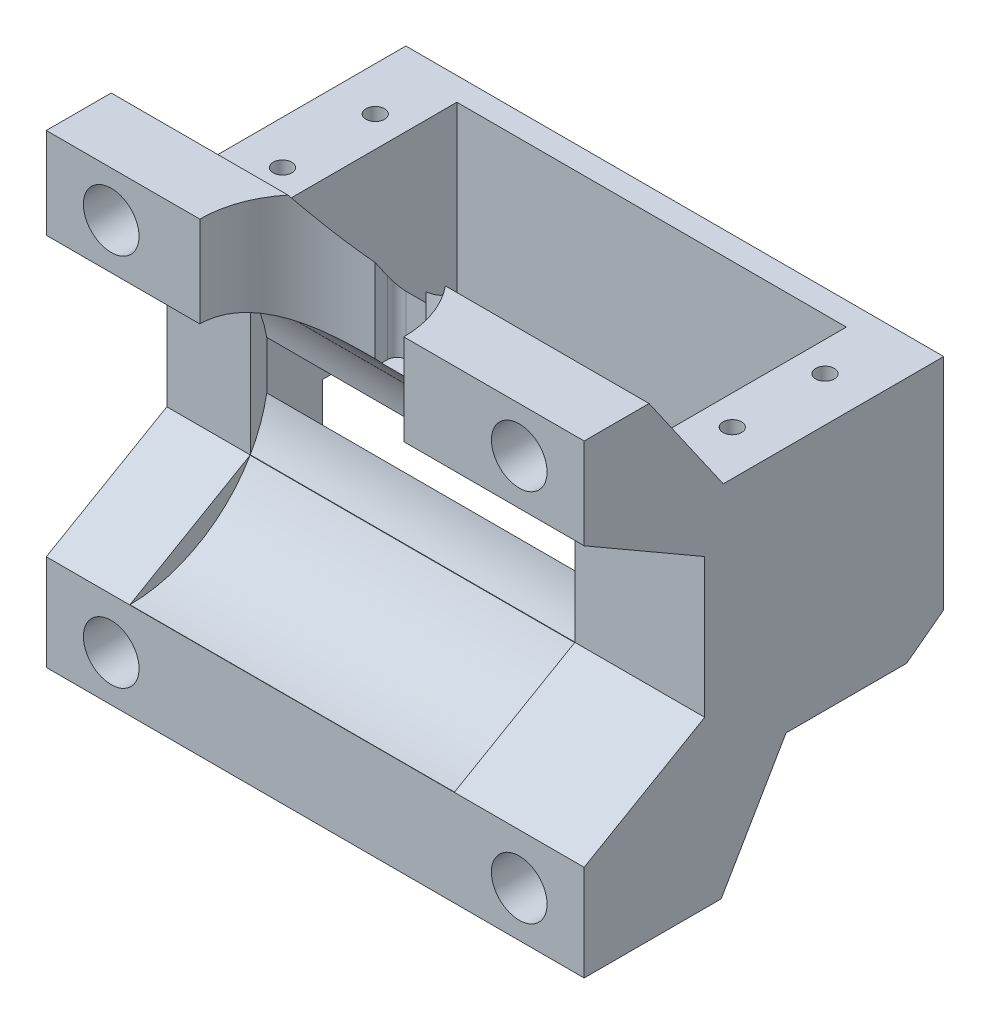
SolidWorks part; units mm, degrees
ref_plane "Front Plane" through (0, 0, 0) normal (0, 0, 1) x (1, 0, 0)
ref_plane "Top Plane" through (0, 0, 0) normal (0, 1, 0) x (1, 0, 0)
ref_plane "Right Plane" through (0, 0, 0) normal (1, 0, 0) x (0, 0, -1)
ref_plane "Plane1" through (0, -30, 0) normal (0, 1, 0) x (1, 0, 0)
sketch "Sketch1" plane through (0, -30, 0) normal (0, 1, 0) x (1, 0, 0)
  line L0 (-4.2598, -25.7738) -> (4.15, -25.7738) construction
  line L1 (29, -25.7738) -> (-29, -25.7738)
  line L2 (29, -25.7738) -> (29, 13)
  line L3 (29, 13) -> (-29, 13)
  line L4 (-29, -25.7738) -> (-29, 13)
  line L5 (29, -25.7738) -> (-29, 13) construction
  line L6 (29, 13) -> (-29, -25.7738) construction
  line L8 (27, 3.8) -> (27, -3.8) construction
  line L9 (-8.46, 10) -> (19.75, 10) construction
  line L10 (-27, -3.8) -> (-27, 3.8) construction
  line L12 (21, 10.5) -> (-21, 10.5)
  line L13 (21, 10.5) -> (21, -11)
  line L14 (21, -11) -> (-21, -11)
  line L15 (-21, 10.5) -> (-21, -11)
  point P0 (0, -6.3869)
  point P9 (-0.0549, -25.7738)
  dimension "D1" = 2
  dimension "D2" = 2.5
  dimension "D3" = 2
  dimension "D4" = 3
  dimension "D5" = 8
  dimension "D6" = 8
  dimension "D7" = 21.5
extrude "Boss-Extrude2" add sketch "Sketch1" along normal up to surface (38.65 mm away)
sketch "Sketch6" plane through (29, 0, 0) normal (1, 0, 0) x (0, 0, -1)
  line L0 (-11, -30) -> (-4, -18)
  line L1 (-25.7738, -30) -> (13, -30) construction
  line L2 (-4, -18) -> (9, -18)
  line L3 (9, -18) -> (13, -15)
  line L4 (13, 8.65) -> (13, -30) construction
  line L5 (13, -15) -> (13, -30)
  line L6 (13, -30) -> (-11, -30)
  dimension "D1" = 24
  dimension "D2" = 17
  dimension "D3" = 12
  dimension "D4" = 3
  dimension "D5" = 4
extrude "Cut-Extrude3" cut sketch "Sketch6" against normal through all
sketch "Sketch7" plane through (0, -18, 0) normal (0, -1, 0) x (1, 0, 0)
  line L0 (-21, -9) -> (-21, 4) construction
  line L1 (-21, -5) -> (-29, -5)
  line L2 (-21, -5) -> (-21, 4)
  line L3 (-21, 4) -> (-29, 4)
  line L4 (-29, -5) -> (-29, 4)
  line L5 (-29, 4) -> (-29, 11) construction
  line L8 (-29, -9) -> (-21, -9) construction
  dimension "D1" = 9
  dimension "D2" = 4
extrude "Cut-Extrude4" cut sketch "Sketch7" against normal blind 8
sketch "Sketch8" plane through (-29, 0, 0) normal (-1, 0, 0) x (0, 0, 1)
  line L0 (25.7738, 8.65) -> (25.7738, -30) construction
  line L1 (25.7738, 10.3611) -> (12.7738, 2.8556)
  line L2 (12.7738, 2.8556) -> (12.7738, -12.1556)
  line L3 (12.7738, -12.1556) -> (25.7738, -19.6611)
  line L4 (25.7738, -19.6611) -> (38.7738, -12.1556)
  line L5 (38.7738, -12.1556) -> (38.7738, 2.8556)
  line L6 (38.7738, 2.8556) -> (25.7738, 10.3611)
  circle A0 centre (25.7738, -4.65) radius 13 construction
  dimension "D1" = 13
sketch "Sketch9" plane through (-29, 0, 0) normal (-1, 0, 0) x (0, 0, 1)
  line L0 (10.7738, 8.65) -> (18.7738, 20.15)
  line L1 (25.7738, 8.65) -> (-13, 8.65) construction
  line L2 (18.7738, 20.15) -> (25.7738, 20.15)
  line L3 (25.7738, 20.15) -> (25.7738, 8.65)
  line L4 (10.7738, 8.65) -> (25.7738, 8.65)
  dimension "D1" = 7
  dimension "D2" = 11.5
  dimension "D3" = 15
extrude "Boss-Extrude3" add sketch "Sketch9" against normal up to surface (58 mm away) up to face at (29, -13.3857, 4.5068)
extrude "Cut-Extrude5" cut sketch "Sketch8" against normal through all
sketch "Sketch10" plane through (0, 20.15, 0) normal (0, 1, 0) x (1, 0, 0)
  line L0 (29, -25.7738) -> (-29, -25.7738) construction
  line L1 (-4.2, -25.7738) -> (1.3, -25.7738)
  line L2 (-4.2, -25.7738) -> (-4.2, -12.7738)
  line L3 (-4.2, -12.7738) -> (1.3, -12.7738)
  line L4 (1.3, -25.7738) -> (1.3, -12.7738)
  circle A0 centre (-1.45, -25.7738) radius 11
  arc A1 (-7.95, -25.7738) -> (5.05, -25.7738) centre (-1.45, -25.7738) ccw construction
  point P11 (-1.45, -12.7738)
  line M7 (29, -18.7738) -> (-29, -18.7738)
  line M9 (-29, -25.7738) -> (29, -25.7738)
  dimension "D1" = 22
  dimension "D2" = 5.5
  dimension "D3" = 13
extrude "Cut-Extrude6" cut sketch "Sketch10" against normal blind 15 contours A0 L4 L3 L2 | A0 L4 M9 M7 | A0 L4 M7 | L4 A0 L2 M7 | A0 L2 M7 M9 | L4 L2 M9 M7 | L2 A0 M7 region at (-1.45, 20.15, 22.2738) region at (-7.9633, 20.15, 22.4652) region at (5.0633, 20.15, 22.4652) region at (-6.3152, 20.15, 17.4069) region at (-1.45, 20.15, 16.8303) region at (3.4152, 20.15, 17.4069) region at (-1.45, 20.15, 13.8342)
fillet "Fillet1" radius 1 2 edges at (1.3, 8.3375, 12.7738) (-4.2, 8.3375, 12.7738)
sketch "Sketch11" plane through (0, 0, 0) normal (1, 0, 0) x (0, 0, -1)
  circle A0 centre (-25.7738, -4.65) radius 15
  dimension "D1" = 30
extrude "Cut-Extrude7" cut sketch "Sketch11" against normal blind 20 and the other way blind 15 contours A0
sketch "Sketch12" plane through (0, 0, 25.7738) normal (0, 0, 1) x (1, 0, 0)
  line L0 (-29, -4.925) -> (29, -4.925) construction
  line L1 (-29, 20.15) -> (-29, 10.3611) construction
  line L2 (29, 20.15) -> (29, 10.3611) construction
  line L3 (-29, -30) -> (29, -30) construction
  line L4 (29, 20.15) -> (9.55, 20.15) construction
  circle A0 centre (-22, 15.2556) radius 3
  circle A1 centre (22, 15.2556) radius 3
  circle A2 centre (22, -25.1056) radius 3
  circle A3 centre (-22, -25.1056) radius 3
  point P14 (-29, 15.2556)
  dimension "D1" = 6
  dimension "D2" = 7
  dimension "D3" = 7
extrude "Cut-Extrude8" cut sketch "Sketch12" against normal blind 20
sketch "Sketch13" plane through (0, 0, 0) normal (0, 0, 1) x (1, 0, 0)
  line L0 (-29, -4.925) -> (29, -4.925) construction
  line L1 (29, 8.65) -> (29, -15) construction
  line L2 (-29, 8.65) -> (-29, -15) construction
  line L3 (29, 20.15) -> (7.0353, 20.15) construction
  line L4 (-21, -30) -> (21, -30) construction
  circle A0 centre (22, 15.2556) radius 4
  circle A1 centre (-22, 15.2556) radius 4
  circle A2 centre (22, -25.1056) radius 4
  circle A3 centre (-22, -25.1056) radius 4
  dimension "D1" = 8
extrude "Cut-Extrude9" cut sketch "Sketch13" along normal blind 20
sketch "Sketch15" plane through (0, 8.65, 0) normal (0, 1, 0) x (1, 0, 0)
  line L0 (29, 13) -> (29, -10.7738) construction
  line L1 (-29, 0) -> (29, 0) construction
  line L2 (-29, -10.7738) -> (-29, 13) construction
  circle A0 centre (-24.3, 5) radius 1
  circle A1 centre (-24.3, -5) radius 1
  circle A2 centre (24.2, 5) radius 1
  circle A3 centre (24.2, -5) radius 1
  point P16 (0, 0)
  dimension "D1" = 2
  dimension "D2" = 2
  dimension "D3" = 48.5
extrude "Cut-Extrude10" cut sketch "Sketch15" against normal blind 10
